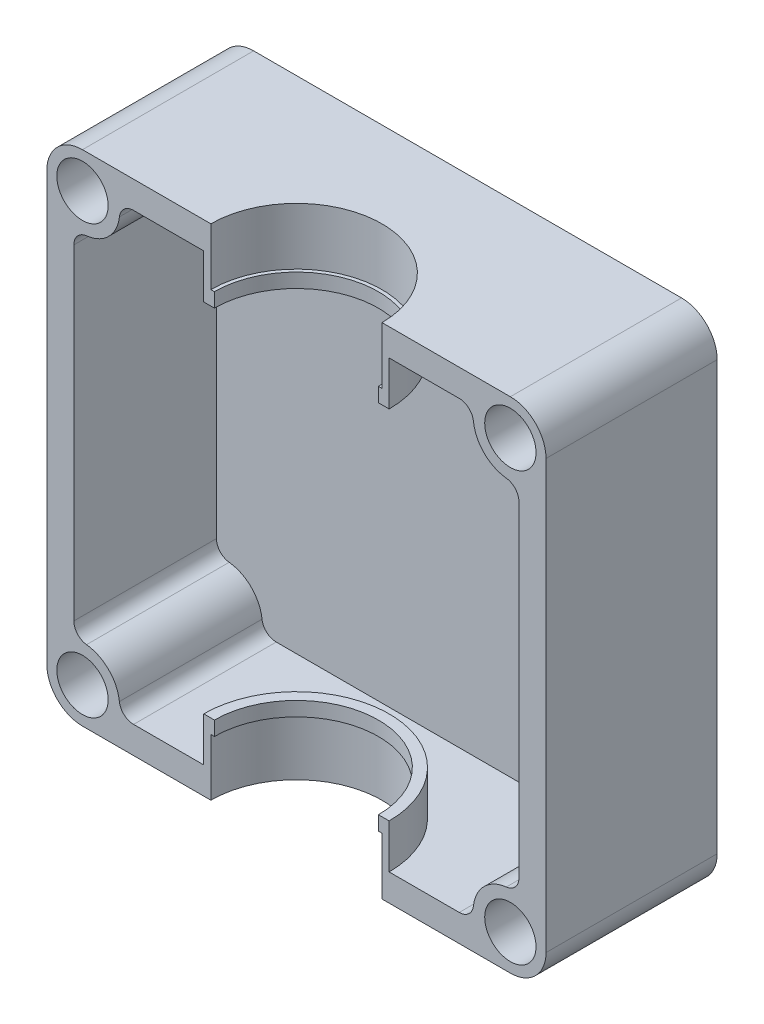
SolidWorks part; units mm, degrees
ref_plane "前视基准面" through (0, 0, 0) normal (0, 0, 1) x (1, 0, 0)
ref_plane "上视基准面" through (0, 0, 0) normal (0, 1, 0) x (1, 0, 0)
ref_plane "右视基准面" through (0, 0, 0) normal (1, 0, 0) x (0, 0, -1)
other "Configuration Table"
sketch "草图1" plane through (0, 0, 0) normal (0, 0, 1) x (-1, 0, 0)
  line L8 (-17.5, 15) -> (-17.5, -15)
  line L9 (-15, -17.5) -> (15, -17.5)
  line L10 (17.5, -15) -> (17.5, 15)
  line L11 (15, 17.5) -> (-15, 17.5)
  line L16 (15.6047, -11.417) -> (15.6047, 11.417)
  line L17 (-11.417, -15.6047) -> (11.417, -15.6047)
  line L18 (-15.6047, 11.417) -> (-15.6047, -11.417)
  line L19 (11.417, 15.6047) -> (-11.417, 15.6047)
  circle A2 centre (-15, -15) radius 1.8
  arc A8 (-15, 17.5) -> (-17.5, 15) centre (-15, 15) ccw
  arc A9 (-17.5, -15) -> (-15, -17.5) centre (-15, -15) ccw
  arc A10 (15, -17.5) -> (17.5, -15) centre (15, -15) ccw
  arc A11 (17.5, 15) -> (15, 17.5) centre (15, 15) ccw
  circle A12 centre (15, -15) radius 1.8
  circle A14 centre (15, 15) radius 1.8
  circle A16 centre (-15, 15) radius 1.8
  arc A38 (12.411, 14.7144) -> (14.7144, 12.411) centre (15, 15) ccw
  arc A39 (15.6047, 11.417) -> (14.7144, 12.411) centre (14.6048, 11.4171) ccw
  arc A40 (14.7144, -12.411) -> (15.6047, -11.417) centre (14.6048, -11.4171) ccw
  arc A41 (14.7144, -12.411) -> (12.411, -14.7144) centre (15, -15) ccw
  arc A42 (11.417, -15.6047) -> (12.411, -14.7144) centre (11.4171, -14.6048) ccw
  arc A43 (-12.411, -14.7144) -> (-11.417, -15.6047) centre (-11.4171, -14.6048) ccw
  arc A44 (-12.411, -14.7144) -> (-14.7144, -12.411) centre (-15, -15) ccw
  arc A45 (-15.6047, -11.417) -> (-14.7144, -12.411) centre (-14.6048, -11.4171) ccw
  arc A46 (-14.7144, 12.411) -> (-15.6047, 11.417) centre (-14.6048, 11.4171) ccw
  arc A47 (-14.7144, 12.411) -> (-12.411, 14.7144) centre (-15, 15) ccw
  arc A48 (-11.417, 15.6047) -> (-12.411, 14.7144) centre (-11.4171, 14.6048) ccw
  arc A49 (12.411, 14.7144) -> (11.417, 15.6047) centre (11.4171, 14.6048) ccw
extrude "凸台-拉伸1" add sketch "草图1" along normal blind 42
sketch "草图2" plane through (0, 17.5, 0) normal (0, 1, 0) x (1, 0, 0)
  line L0 (0, 0) -> (0, -12)
  circle A0 centre (0, -12) radius 6
  dimension "D2" = 12
  dimension "D1" = 12
extrude "切除-拉伸1" cut sketch "草图2" against normal through all contours A0 region at (-4.1226, 17.5, 16.1226)
sketch "草图3" plane through (-17.5, 0, 0) normal (-1, 0, 0) x (0, 0, 1)
  line L0 (0, 0) -> (30, 0)
  circle A0 centre (30, 0) radius 6
  dimension "D2" = 12
  dimension "D1" = 30
extrude "切除-拉伸2" cut sketch "草图3" against normal through all contours A0 region at (-17.5, -5.8303, 30)
sketch "草图4" plane through (0, 17.5, 0) normal (0, 1, 0) x (1, 0, 0)
  line L0 (6, -12) -> (-20.6979, -12)
  line L1 (-20.6979, -12) -> (-20.6979, -44.8932)
  line L2 (-20.6979, -44.8932) -> (22.0868, -44.8932)
  line L3 (22.0868, -44.8932) -> (22.0868, -12)
  line L4 (22.0868, -12) -> (6, -12)
  circle A0 centre (0, -12) radius 6 construction
extrude "切除-拉伸3" cut sketch "草图4" against normal through all
sketch "草图5" plane through (0, -15.6047, 0) normal (0, 1, 0) x (1, 0, 0)
  line L0 (-6, -12) -> (-6.5, -12)
  line L1 (6.5, -12) -> (6, -12)
  arc A0 (6.5, -12) -> (-6.5, -12) centre (0, -12) ccw
  arc A1 (6, -12) -> (-6, -12) centre (0, -12) ccw
  dimension "D1" = 13
extrude "凸台-拉伸2" add sketch "草图5" along normal blind 3.1
ref_plane "基准面1" through (0, 0, 0) normal (0, 1, 0) x (1, 0, 0)
sketch "草图7" plane through (0, -12.5047, 0) normal (0, 1, 0) x (1, 0, 0)
  line L0 (6.5, -12) -> (5.75, -12)
  line L2 (-5.75, -12) -> (-6.5, -12)
  arc A0 (6.5, -12) -> (-6.5, -12) centre (0, -12) ccw
  arc A1 (5.75, -12) -> (-5.75, -12) centre (0, -12) ccw
  dimension "D1" = 13
  dimension "D2" = 11.5
extrude "凸台-拉伸3" add sketch "草图7" against normal blind 1
mirror "镜向2" about plane through (0, 0, 0) normal (0, 1, 0) of "凸台-拉伸3", "凸台-拉伸2"
sketch "草图8" plane through (0, 0, 0) normal (0, 0, -1) x (-1, 0, 0)
  line L5 (-11.417, -15.6047) -> (11.417, -15.6047)
  line L6 (-15.6047, 11.417) -> (-15.6047, -11.417)
  line L7 (11.417, 15.6047) -> (-11.417, 15.6047)
  line L12 (15.6047, -11.417) -> (15.6047, 11.417)
  line L13 (-11.417, -15.6047) -> (11.417, -15.6047)
  line L14 (-15.6047, 11.417) -> (-15.6047, -11.417)
  line L15 (11.417, 15.6047) -> (-11.417, 15.6047)
  line L16 (15.6047, -11.417) -> (15.6047, 11.417)
  arc A21 (11.417, -15.6047) -> (12.411, -14.7144) centre (11.4171, -14.6048) ccw
  arc A22 (-12.411, -14.7144) -> (-11.417, -15.6047) centre (-11.4171, -14.6048) ccw
  arc A23 (-12.411, -14.7144) -> (-14.7144, -12.411) centre (-15, -15) ccw
  arc A24 (-15.6047, -11.417) -> (-14.7144, -12.411) centre (-14.6048, -11.4171) ccw
  arc A25 (-14.7144, 12.411) -> (-15.6047, 11.417) centre (-14.6048, 11.4171) ccw
  arc A26 (-14.7144, 12.411) -> (-12.411, 14.7144) centre (-15, 15) ccw
  arc A27 (-11.417, 15.6047) -> (-12.411, 14.7144) centre (-11.4171, 14.6048) ccw
  arc A28 (12.411, 14.7144) -> (11.417, 15.6047) centre (11.4171, 14.6048) ccw
  arc A29 (12.411, 14.7144) -> (14.7144, 12.411) centre (15, 15) ccw
  arc A30 (15.6047, 11.417) -> (14.7144, 12.411) centre (14.6048, 11.4171) ccw
  arc A31 (14.7144, -12.411) -> (15.6047, -11.417) centre (14.6048, -11.4171) ccw
  arc A32 (14.7144, -12.411) -> (12.411, -14.7144) centre (15, -15) ccw
  arc A33 (11.417, -15.6047) -> (12.411, -14.7144) centre (11.4171, -14.6048) ccw
  arc A34 (-12.411, -14.7144) -> (-11.417, -15.6047) centre (-11.4171, -14.6048) ccw
  arc A35 (-12.411, -14.7144) -> (-14.7144, -12.411) centre (-15, -15) ccw
  arc A36 (-15.6047, -11.417) -> (-14.7144, -12.411) centre (-14.6048, -11.4171) ccw
  arc A37 (-14.7144, 12.411) -> (-15.6047, 11.417) centre (-14.6048, 11.4171) ccw
  arc A38 (-14.7144, 12.411) -> (-12.411, 14.7144) centre (-15, 15) ccw
  arc A39 (-11.417, 15.6047) -> (-12.411, 14.7144) centre (-11.4171, 14.6048) ccw
  arc A40 (12.411, 14.7144) -> (11.417, 15.6047) centre (11.4171, 14.6048) ccw
  arc A41 (12.411, 14.7144) -> (14.7144, 12.411) centre (15, 15) ccw
  arc A42 (15.6047, 11.417) -> (14.7144, 12.411) centre (14.6048, 11.4171) ccw
  arc A43 (14.7144, -12.411) -> (15.6047, -11.417) centre (14.6048, -11.4171) ccw
  arc A44 (14.7144, -12.411) -> (12.411, -14.7144) centre (15, -15) ccw
  dimension "D1" = 0
extrude "凸台-拉伸4" add sketch "草图8" against normal blind 2
